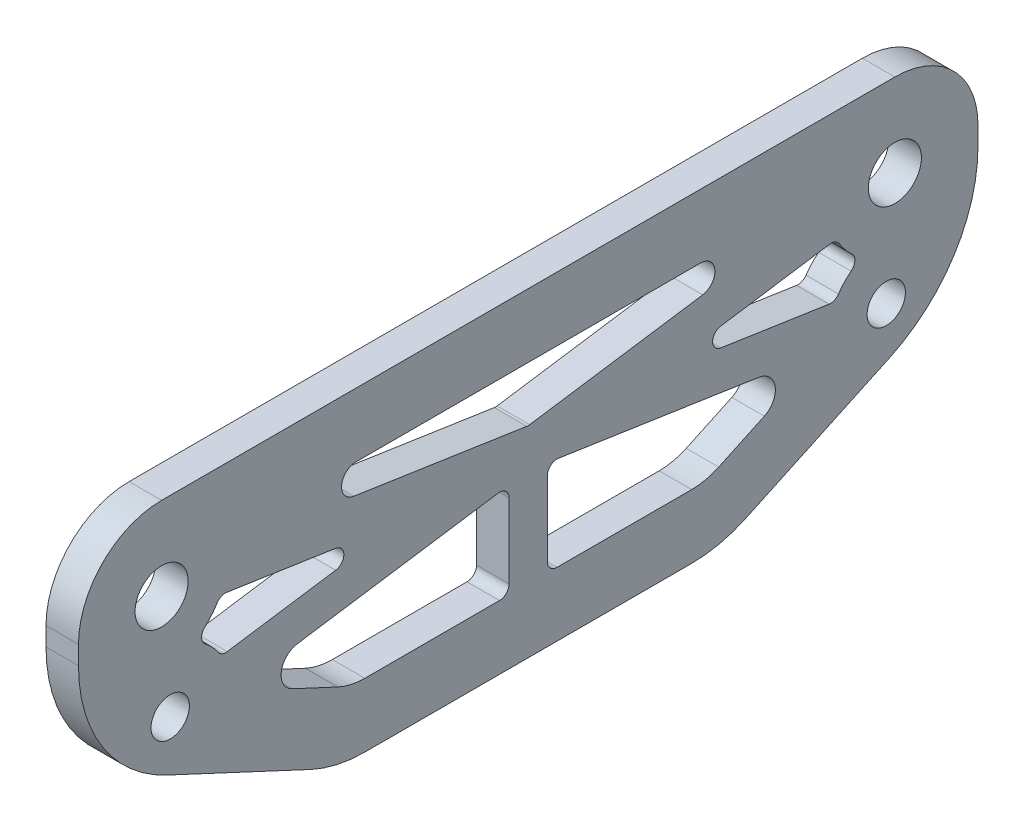
SolidWorks part; units mm, degrees
ref_plane "Front Plane" through (0, 0, 0) normal (0, 0, 1) x (1, 0, 0)
ref_plane "Top Plane" through (0, 0, 0) normal (0, 1, 0) x (1, 0, 0)
ref_plane "Right Plane" through (0, 0, 0) normal (1, 0, 0) x (0, 0, -1)
sketch "Sketch1" plane through (0, 0, 0) normal (1, 0, 0) x (0, 0, -1)
  line L0 (15, 12.5) -> (28.675, 12.5)
  line L1 (-15, -12.5) -> (15, -12.5)
  line L3 (-15, 12.5) -> (15, 12.5)
  line L5 (-15, -12.5) -> (15, 12.5) construction
  line L6 (-15, 12.5) -> (15, -12.5) construction
  line L8 (0, 12.5) -> (0, -12.5) construction
  line L10 (-15, 12.5) -> (-28.675, 12.5)
  line L11 (23.175, 191.5713) -> (23.175, -35.8287) construction
  line L13 (35.175, 6) -> (35.175, 4.5526)
  line L14 (28.2464, -6.3231) -> (15, -12.5)
  line L16 (-35.175, 6) -> (-35.175, 4.5526)
  line L17 (-28.2464, -6.3231) -> (-15, -12.5)
  arc A0 (28.675, 12.5) -> (35.175, 6) centre (28.675, 6) cw
  circle A1 centre (28.675, 6) radius 5.5 construction
  circle A2 centre (-28.675, 6) radius 5.5 construction
  arc A3 (-28.675, 12.5) -> (-35.175, 6) centre (-28.675, 6) ccw
  arc A4 (35.175, 4.5526) -> (28.2464, -6.3231) centre (23.175, 4.5526) cw
  circle A5 centre (28.675, 6) radius 2.075
  arc A6 (-35.175, 4.5526) -> (-28.2464, -6.3231) centre (-23.175, 4.5526) ccw
  circle A9 centre (-28.675, 6) radius 2.075
  circle A11 centre (28, -2.5) radius 1.5
  circle A12 centre (-28, -2.5) radius 1.5
  point P0 (0, 0)
  point P28 (0, 0)
  dimension "D1" = 11
  dimension "D2" = 1
  dimension "D3" = 4.15
  dimension "D4" = 3
  dimension "D6" = 25
  dimension "D8" = 12
  dimension "D5" = 25
  dimension "D7" = 30
  dimension "D9" = 28
  dimension "D10" = 2.5
extrude "Boss-Extrude1" add sketch "Sketch1" along normal blind 2.54
fillet "Fillet1" radius 10 2 edges at (1.27, -12.5, -15) (1.27, -12.5, 15)
sketch "Sketch2" plane through (0, 0, 0) normal (1, 0, 0) x (0, 0, -1)
  line L0 (-28.675, 6) -> (28, -2.5) construction
  line L10 (-28.675, -2.6012) -> (28.675, 6)
  line L11 (-28.675, 6) -> (28, -2.5)
  line L12 (-28.8975, 4.5166) -> (27.7775, -3.9834)
  line L13 (-28.4525, 7.4834) -> (28.2225, -1.0166)
  line L14 (-28.8975, 4.5166) -> (-28.4525, 7.4834)
  line L15 (27.7775, -3.9834) -> (28.2225, -1.0166)
  line L16 (-12.7831, -7.5) -> (12.7831, -7.5)
  line L17 (14.8961, -7.0315) -> (26.1333, -1.7916)
  line L18 (30.175, 4.5526) -> (30.175, 6)
  line L19 (28.675, 7.5) -> (-28.675, 7.5)
  line L20 (-30.175, 6) -> (-30.175, 4.5526)
  line L21 (-26.1333, -1.7916) -> (-14.8961, -7.0315)
  line L22 (-12.7831, -7.5) -> (12.7831, -7.5)
  line L23 (14.8961, -7.0315) -> (26.1333, -1.7916)
  line L24 (30.175, 4.5526) -> (30.175, 6)
  line L25 (28.675, 7.5) -> (-28.675, 7.5)
  line L26 (-30.175, 6) -> (-30.175, 4.5526)
  line L27 (-26.1333, -1.7916) -> (-14.8961, -7.0315)
  line L28 (-28.4525, -4.0846) -> (28.8975, 4.5166)
  line L29 (-28.8975, -1.1178) -> (28.4525, 7.4834)
  line L30 (-28.4525, -4.0846) -> (-28.8975, -1.1178)
  line L31 (28.8975, 4.5166) -> (28.4525, 7.4834)
  line L32 (0, -7.5) -> (0, 7.5) construction
  line L33 (0, 1.6994) -> (0, -7.5)
  line L34 (-1.5, 1.6994) -> (-1.5, -7.5)
  line L35 (1.5, 1.6994) -> (1.5, -7.5)
  line L36 (-1.5, 1.6994) -> (1.5, 1.6994)
  line L37 (-1.5, -7.5) -> (1.5, -7.5)
  arc A0 (-18.0527, -2.5249) -> (-18.4641, -5.3678) centre (-17.8302, -4.0083) ccw
  arc A1 (18.0527, -2.5249) -> (18.4641, -5.3678) centre (17.8302, -4.0083) cw
  circle A2 centre (-28, -2.5) radius 4.5
  circle A3 centre (-28, -2.5) radius 4.5
  circle A5 centre (28, -2.5) radius 4.5
  circle A6 centre (28, -2.5) radius 4.5
  circle A11 centre (-28.675, 6) radius 5.075
  arc A12 (12.7831, -7.5) -> (14.8961, -7.0315) centre (12.7831, -2.5) ccw
  arc A13 (26.1333, -1.7916) -> (30.175, 4.5526) centre (23.175, 4.5526) ccw
  arc A14 (30.175, 6) -> (28.675, 7.5) centre (28.675, 6) ccw
  arc A15 (-28.675, 7.5) -> (-30.175, 6) centre (-28.675, 6) ccw
  arc A16 (-30.175, 4.5526) -> (-26.1333, -1.7916) centre (-23.175, 4.5526) ccw
  arc A17 (-14.8961, -7.0315) -> (-12.7831, -7.5) centre (-12.7831, -2.5) ccw
  arc A18 (12.7831, -7.5) -> (14.8961, -7.0315) centre (12.7831, -2.5) ccw
  arc A19 (26.1333, -1.7916) -> (30.175, 4.5526) centre (23.175, 4.5526) ccw
  arc A20 (30.175, 6) -> (28.675, 7.5) centre (28.675, 6) ccw
  arc A21 (-28.675, 7.5) -> (-30.175, 6) centre (-28.675, 6) ccw
  arc A22 (-30.175, 4.5526) -> (-26.1333, -1.7916) centre (-23.175, 4.5526) ccw
  arc A23 (-14.8961, -7.0315) -> (-12.7831, -7.5) centre (-12.7831, -2.5) ccw
  circle A24 centre (-28.675, 6) radius 5.075
  circle A26 centre (28.675, 6) radius 5.075
  circle A27 centre (28.675, 6) radius 5.075
  arc A32 (13.477, 7.5) -> (13.6439, 5.2624) centre (13.477, 6.375) cw
  arc A33 (-13.477, 7.5) -> (-13.6439, 5.2624) centre (-13.477, 6.375) ccw
  dimension "D11" = 3
  dimension "D12" = 1.125
  dimension "D2" = 1.5
  dimension "D1" = 5
  dimension "D3" = 3
  dimension "D4" = 3
  dimension "D6" = 1.5
  dimension "D7" = 1.5
  dimension "D8" = 1.5
  dimension "D9" = 1.5
  dimension "D13" = 1.5
  dimension "D14" = 1.5
  dimension "D15" = 3
extrude "Cut-Extrude2" cut sketch "Sketch2" along normal through all contours A24 A3 L29 L12 | A27 L28 L13 A6 | L25 A33 L13 L29 A32 | A1 L12 L35 L22 | L28 A0 L22 L34 region at (0, 1.7005, 19.9688) region at (0, -4.2389, 9.1911) region at (0, 5.8357, 0) region at (0, -4.2389, -9.1911) region at (0, 1.7005, -19.9688)
fillet "Fillet2" radius 0.75 13 edges at (1.27, -7.5, -1.5) (1.27, 3.7975, -24.1028) (1.27, 1.6994, -10.1133) (1.27, 3.7975, 24.1028) (1.27, 3.2162, 0) (1.27, -0.0424, -1.5) (1.27, -7.5, 1.5) (1.27, -0.0424, 1.5) (1.27, 1.6994, 10.1133) (1.27, -0.3873, -24.0268) (1.27, 1.6002, -26.1457) (1.27, -0.3873, 24.0268) (1.27, 1.6002, 26.1457)
